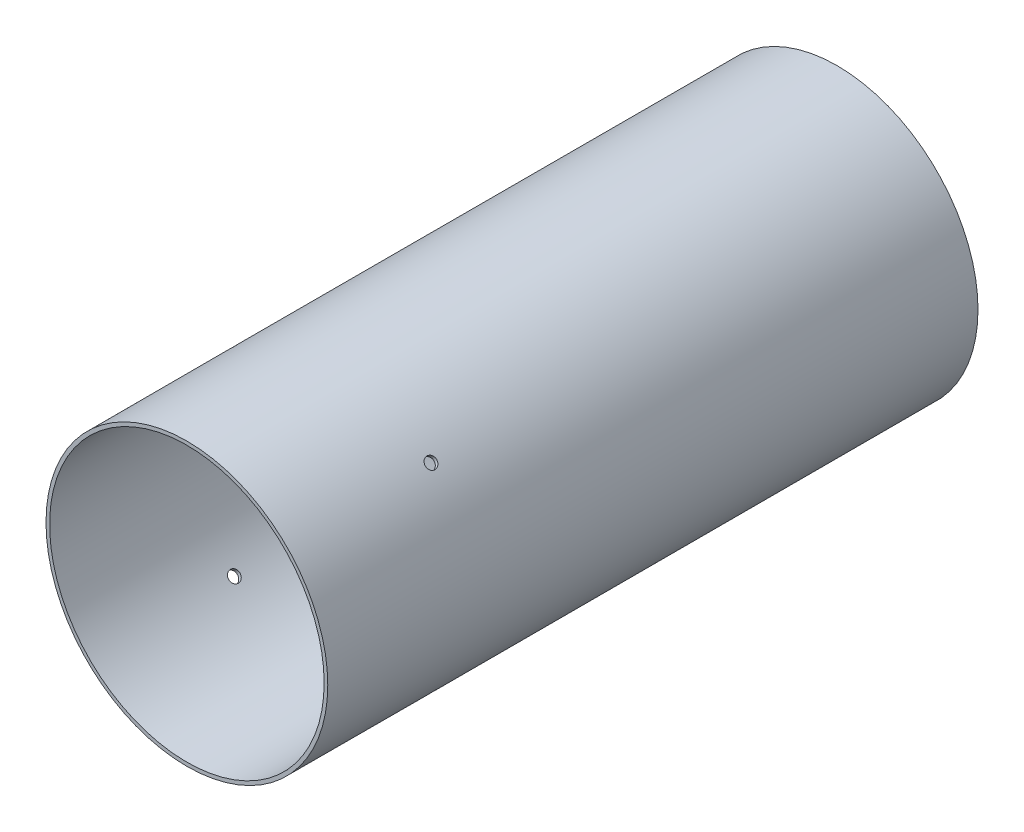
SolidWorks part; units mm, degrees
ref_plane "Front Plane" through (0, 0, 0) normal (0, 0, 1) x (1, 0, 0)
ref_plane "Top Plane" through (0, 0, 0) normal (0, 1, 0) x (1, 0, 0)
ref_plane "Right Plane" through (0, 0, 0) normal (1, 0, 0) x (0, 0, -1)
sketch "Sketch1" plane through (0, 0, 0) normal (0, 0, 1) x (1, 0, 0)
  circle A0 centre (0, 0) radius 49.53
  circle A1 centre (0, 0) radius 48.26
  dimension "D1" = 99.06
  dimension "D2" = 96.52
extrude "Boss-Extrude1" add sketch "Sketch1" along normal blind 228.6
extrude "Cut-Extrude1" cut sketch "Sketch2" against normal blind 12.7
sketch "Sketch2" plane through (-120.5803, -48.7382, -78.9954) normal (-0.7071, 0.7071, 0) x (0.7071, 0.7071, 0)
  circle A0 centre (119.7263, -256.7954) radius 1.9844
pattern_circular "CirPattern1" count 4 over 360 of "Cut-Extrude1"
extrude "Cut-Extrude2" cut sketch "Sketch3" against normal blind 25.4
sketch "Sketch3" plane through (-108.0218, -85.4992, -79.3332) normal (-0.866, 0.5, 0) x (0, 0, 1)
  circle A0 centre (196.8082, 128.0554) radius 2.3813
  circle A1 centre (190.4582, 128.0554) radius 2.3813
  point P3 (0, 0)
  point P6 (0, 0)
  point P8 (0, 0)
